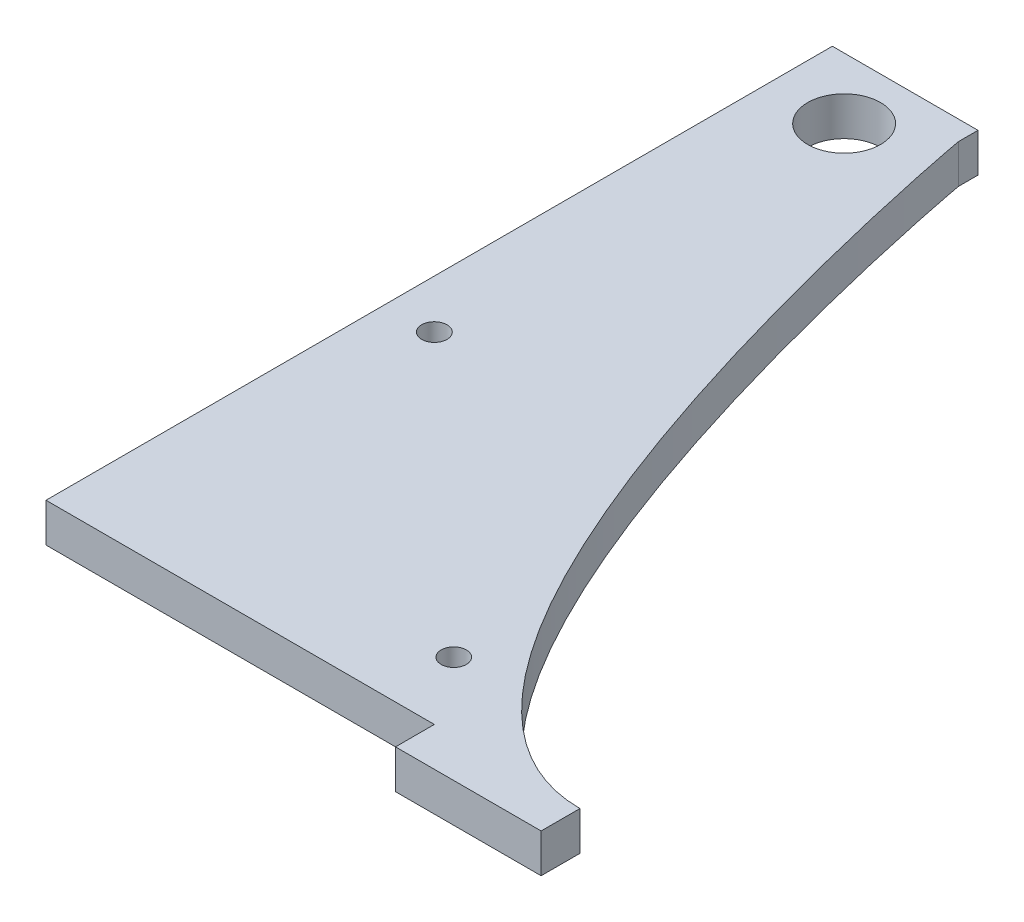
SolidWorks part; units mm, degrees
ref_plane "Front Plane" through (0, 0, 0) normal (0, 0, 1) x (1, 0, 0)
ref_plane "Top Plane" through (0, 0, 0) normal (0, 1, 0) x (1, 0, 0)
ref_plane "Right Plane" through (0, 0, 0) normal (1, 0, 0) x (0, 0, -1)
sketch "Sketch1" plane through (0, 0, 0) normal (0, 1, 0) x (1, 0, 0)
  line L0 (9.525, -53.975) -> (60.325, -53.975) construction
  line L1 (-9.525, -53.975) -> (9.525, -53.975) construction
  line L2 (-9.525, -53.975) -> (-9.525, 53.975) construction
  line L3 (-9.525, 53.975) -> (9.525, 53.975)
  line L4 (9.525, -53.975) -> (9.525, 53.975) construction
  line L5 (-9.525, -53.975) -> (9.525, 53.975) construction
  line L6 (-9.525, 53.975) -> (9.525, -53.975) construction
  line L7 (0, 53.975) -> (0, 45.9867) construction
  line L8 (-9.525, 50.7492) -> (9.525, 50.7492) construction
  line L9 (9.525, 51.435) -> (9.525, 53.975)
  line L10 (60.325, -53.975) -> (60.325, -48.895) construction
  line L11 (60.325, -48.895) -> (-9.525, -48.895) construction
  line L12 (60.325, -53.975) -> (60.325, -48.895) construction
  line L13 (60.325, -48.895) -> (-9.525, -48.895)
  line L14 (-9.525, -48.895) -> (-9.525, 53.975)
  line L15 (31.115, -19.685) -> (31.115, -48.895) construction
  circle A0 centre (0, 45.9867) radius 4.7625
  spline S0 degree 3 poles (9.525, 51.435) (9.525, 51.2145) (27.8191, -48.895) (60.325, -48.895) knots 0 0 0 0 1 1 1 1
  point P4 (0, 0)
  dimension "D5" = 9.525
  dimension "D1" = 107.95
  dimension "D2" = 19.05
  dimension "D3" = 50.8
  dimension "D4" = 2.54
  dimension "D6" = 104.7242
  dimension "D7" = 5.08
  dimension "D8" = 40.64
  dimension "D9" = 29.21
extrude "Boss-Extrude1" add sketch "Sketch1" along normal blind 5.08
sketch "Sketch4" plane through (0, 5.08, 0) normal (0, 1, 0) x (1, 0, 0)
  line L0 (-9.525, 53.975) -> (-9.525, -48.895) construction
  line L1 (60.325, -48.895) -> (41.275, -48.895)
  line L2 (60.325, -48.895) -> (60.325, -53.975)
  line L3 (60.325, -53.975) -> (41.275, -53.975)
  line L4 (41.275, -48.895) -> (41.275, -53.975)
  line L5 (60.325, -48.895) -> (41.275, -53.975) construction
  line L6 (60.325, -53.975) -> (41.275, -48.895) construction
  point P4 (50.8, -51.435)
  dimension "D1" = 50.8
  dimension "D2" = 5.08
extrude "Boss-Extrude2" add sketch "Sketch4" against normal up to surface (5.08 mm away) up to face at (17.145, 0, -2.286)
sketch "Sketch5" plane through (0, 0, 0) normal (0, -1, 0) x (1, 0, 0)
  circle A1 centre (34.925, 40.005) radius 1.651
  circle A3 centre (-3.175, 4.445) radius 1.6607
extrude "Cut-Extrude1" cut sketch "Sketch5" against normal through all both
